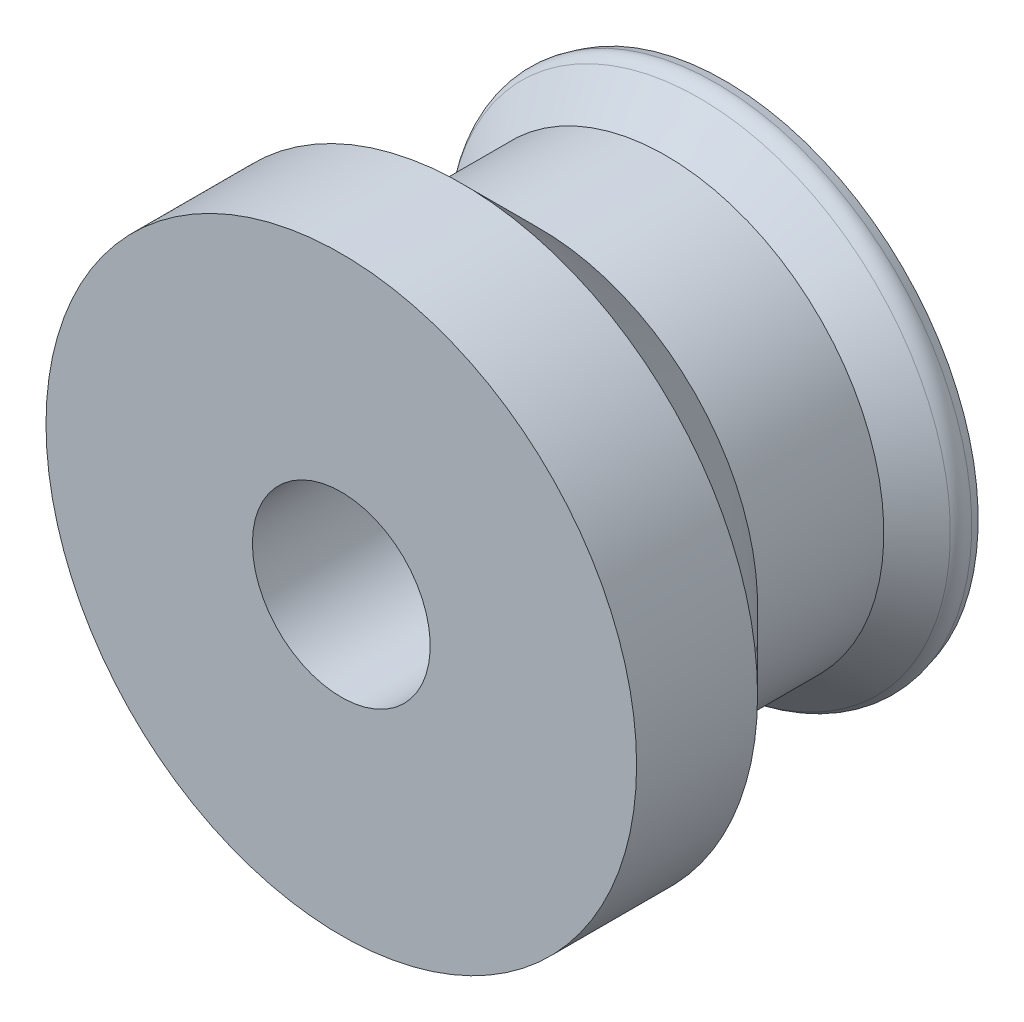
SolidWorks part; units mm, degrees
material "ABS"
ref_plane "Front Plane" through (0, 0, 0) normal (0, 0, 1) x (1, 0, 0)
ref_plane "Top Plane" through (0, 0, 0) normal (0, 1, 0) x (1, 0, 0)
ref_plane "Right Plane" through (0, 0, 0) normal (1, 0, 0) x (0, 0, -1)
ref_plane "Plane1" through (0, -64.3208, 0) normal (0, -1, 0) x (1, 0, 0)
sketch "Sketch1" plane through (0, -64.3208, 0) normal (0, -1, 0) x (1, 0, 0)
  line L0 (114.7703, 11) -> (106.3006, 11)
  line L1 (106.3006, 11) -> (106.3006, 0)
  line L2 (106.3006, 0) -> (113.5675, 0)
  line L3 (113.5675, 0) -> (113.6349, 0.2515)
  line L4 (113.5055, 0.7345) -> (112.5506, 1.6893)
  line L5 (112.5506, 1.6893) -> (112.5506, 5.3107)
  line L6 (112.5506, 5.3107) -> (114.7703, 7.5303)
  line L7 (114.7703, 7.5303) -> (114.7703, 11)
  line L8 (106.3006, 11) -> (106.3006, 0) construction
  arc A0 (113.6349, 0.2515) -> (113.5055, 0.7345) centre (113.152, 0.3809) ccw
revolve "Revolve1" add sketch "Sketch1" angle 360 about L8 reverse direction yes
hole_wizard "Ø5.1 (5.1) Diameter Hole1" positions "Sketch3" profile "Sketch2" hole size "Ø5.1" standard "ANSI Metric"
sketch "Sketch3" plane through (0, 0, 0) normal (0, 0, -1) x (-1, 0, 0)
  point P0 (-106.3006, -64.3208)
sketch "Sketch2" plane through (106.3006, -64.3208, 0) normal (1, 0, 0) x (0, 1, 0)
  line L0 (0, 0) -> (0, 11)
  line L1 (0, 11) -> (2.55, 11)
  line L2 (2.55, 11) -> (2.55, 0)
  line L5 (2.55, 0) -> (0, 0)
  line L11 (0, -6.35) -> (0, 107.95) construction
  dimension "Thru Hole Dia." = 5.1
  dimension "Thru Hole Depth" = 11
ref_axis "Axis1" through (106.3006, -64.3208, 11) along (0, 0, -1)
